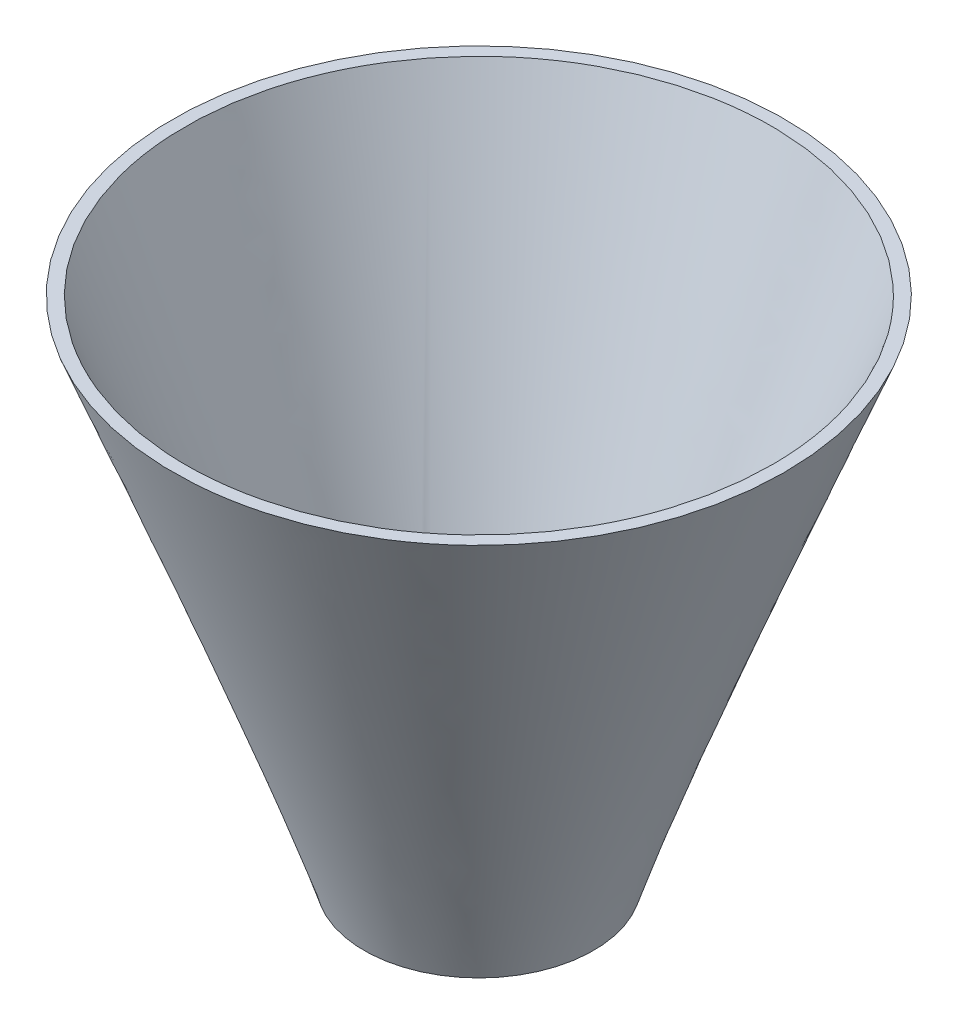
SolidWorks part; units mm, degrees
ref_plane "前视基准面" through (0, 0, 0) normal (0, 0, 1) x (1, 0, 0)
ref_plane "上视基准面" through (0, 0, 0) normal (0, 1, 0) x (1, 0, 0)
ref_plane "右视基准面" through (0, 0, 0) normal (1, 0, 0) x (0, 0, -1)
other "Configuration Table"
sketch "草图5" plane through (0, 0, 0) normal (0, 1, 0) x (1, 0, 0)
  circle A1 centre (0, 0) radius 9
ref_plane "基准面3" through (0, 40, 0) normal (0, 1, 0) x (1, 0, 0)
sketch "草图6" plane through (0, 40, 0) normal (0, 1, 0) x (1, 0, 0)
  circle A1 centre (0, 0) radius 24
loft "放样2" add profiles "草图6", "草图5" connector at (-9.7663, 40, -21.923) connector at (-6.7734, 0, -5.9263)
sketch "草图9" plane through (0, 0, 0) normal (0, -1, 0) x (1, 0, 0)
  circle A0 centre (0, 0) radius 8.1
sketch "草图10" plane through (0, 40, 0) normal (0, 1, 0) x (1, 0, 0)
  circle A0 centre (0, 0) radius 23
loft "切除-放样2" cut profiles "草图9", "草图10" connector at (-7.518, 0, -3.0149) connector at (-18.1025, 40, -14.188)
